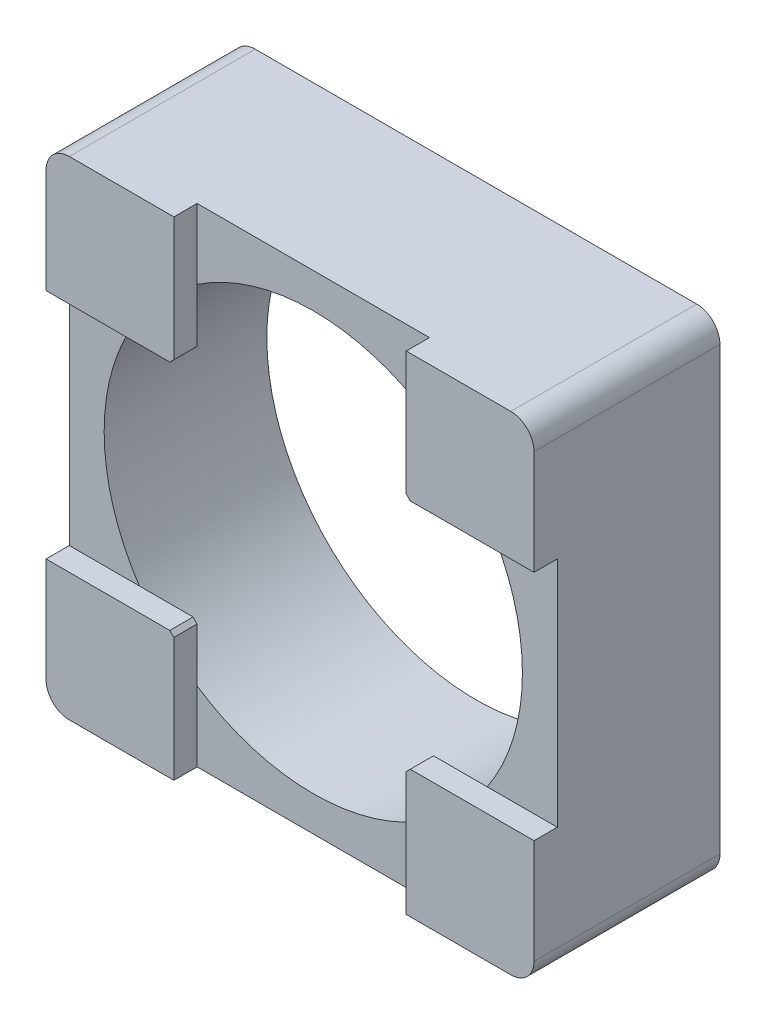
SolidWorks part; units mm, degrees
ref_plane "Top Plane" through (0, 0, 0) normal (0, 0, 1) x (1, 0, 0)
ref_plane "Right Plane" through (0, 0, 0) normal (0, 1, 0) x (1, 0, 0)
ref_plane "Front Plane" through (0, 0, 0) normal (1, 0, 0) x (0, 0, -1)
sketch "Sketch1" plane through (0, 0, 0) normal (0, 0, 1) x (1, 0, 0)
  line L0 (-10.5, 10.5) -> (10.5, -10.5) construction
  line L1 (-10.5, 10.5) -> (10.5, 10.5)
  line L2 (-10.5, 10.5) -> (-10.5, -10.5)
  line L3 (-10.5, -10.5) -> (10.5, -10.5)
  line L4 (10.5, 10.5) -> (10.5, -10.5)
  circle A0 centre (0, 0) radius 9
  circle A1 centre (0, 0) radius 7.1953 construction
  dimension "D1" = 18
  dimension "D2" = 21
extrude "Boss-Extrude1" add sketch "Sketch1" along normal mid plane 8
sketch "Sketch2" plane through (0, 0, 4) normal (0, 0, 1) x (1, 0, 0)
  circle A0 centre (0, 0) radius 9 construction
  circle A1 centre (0, 0) radius 9
  circle A2 centre (0, 0) radius 7.1953 construction
  circle A3 centre (0, 0) radius 7.1953
extrude "Boss-Extrude2" add sketch "Sketch2" against normal blind 1
sketch "Sketch3" plane through (0, 0, 4) normal (0, 0, 1) x (1, 0, 0)
  line L0 (-10.5, -5) -> (-5.1743, -5)
  line L1 (-10.5, 0) -> (-7.1953, 0) construction
  line L2 (-10.5, 5) -> (-5.1743, 5)
  line L3 (-5, 10.5) -> (-5, 5.1743)
  line L4 (-10.5, 10.5) -> (-10.5, -10.5)
  line L5 (-10.5, -10.5) -> (10.5, -10.5)
  line L6 (10.5, -10.5) -> (10.5, 10.5)
  line L7 (10.5, 10.5) -> (-10.5, 10.5)
  line L8 (-10.5, 5) -> (-10.5, -5)
  line L9 (-5, -10.5) -> (5, -10.5)
  line L10 (10.5, -5) -> (10.5, 5)
  line L11 (5, 10.5) -> (-5, 10.5)
  line L12 (5, 10.5) -> (5, 5.1743)
  line L13 (10.5, 5) -> (5.1743, 5)
  line L14 (10.5, -5) -> (5.1743, -5)
  line L15 (5, -10.5) -> (5, -5.1743)
  line L16 (-5, -10.5) -> (-5, -5.1743)
  line L17 (7.1953, 0) -> (10.5, 0) construction
  circle A0 centre (0, 0) radius 7.1953 construction
  arc A1 (-5, 5.1743) -> (-5.1743, 5) centre (0, 0) ccw
  arc A2 (-5.1743, -5) -> (-5, -5.1743) centre (0, 0) ccw
  arc A3 (5, -5.1743) -> (5.1743, -5) centre (0, 0) ccw
  arc A4 (5.1743, 5) -> (5, 5.1743) centre (0, 0) ccw
  point P28 (0, 0)
  dimension "D2" = 10
  dimension "D1" = 0
  dimension "D3" = 4
extrude "Cut-Extrude1" cut sketch "Sketch3" against normal blind 1
fillet "Fillet1" radius 1 4 edges at (-10.5, 10.5, 0) (-10.5, -10.5, 0) (10.5, 10.5, 0) (10.5, -10.5, 0)
